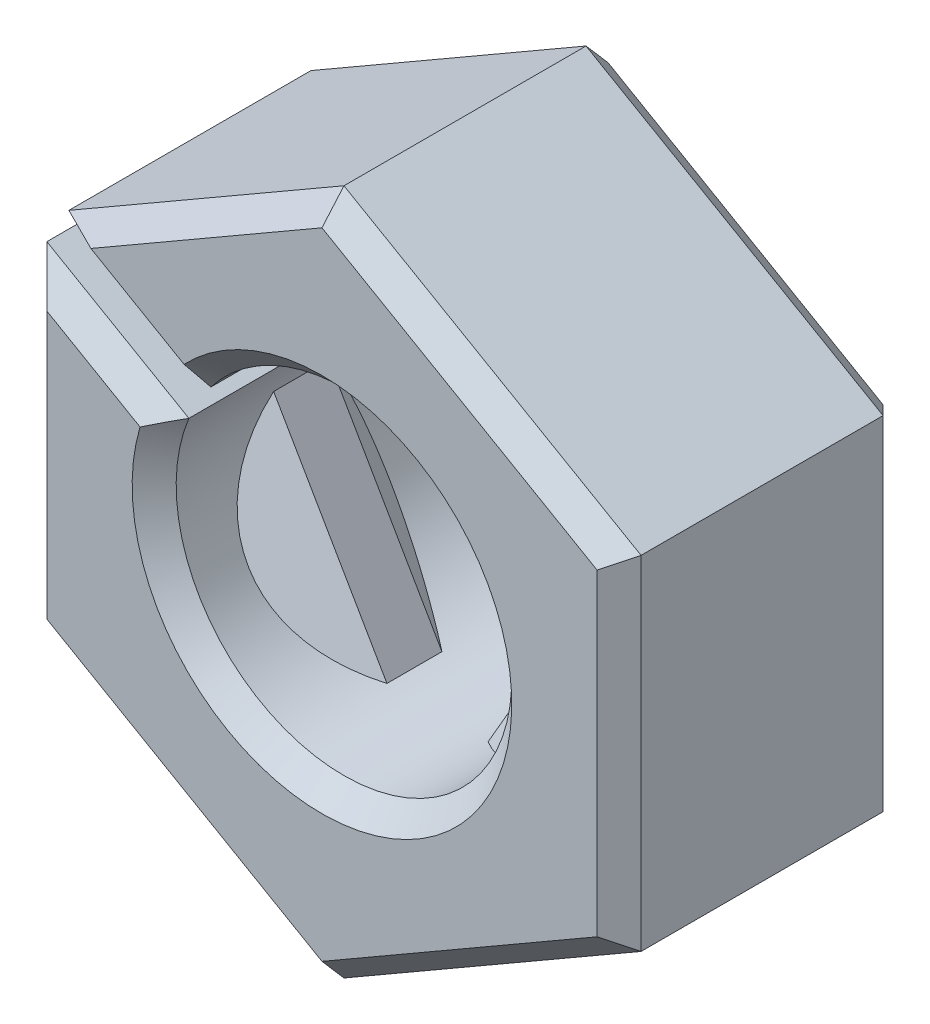
SolidWorks part; units mm, degrees
ref_plane "Front" through (0, 0, 0) normal (0, 0, 1) x (1, 0, 0)
ref_plane "Top" through (0, 0, 0) normal (0, 1, 0) x (1, 0, 0)
ref_plane "Right" through (0, 0, 0) normal (1, 0, 0) x (0, 0, -1)
sketch "Sketch1" plane through (0, 0, 0) normal (0, 0, 1) x (1, 0, 0)
  line L1 (2.7, -1.5588) -> (2.7, 1.5588)
  line L2 (2.7, 1.5588) -> (0, 3.1177)
  line L3 (0, 3.1177) -> (-2.7, 1.5588)
  line L4 (-2.7, 1.5588) -> (-2.7, -1.5588)
  line L5 (-2.7, -1.5588) -> (0, -3.1177)
  line L6 (0, -3.1177) -> (2.7, -1.5588)
  circle A0 centre (0, 0) radius 2.7 construction
  circle A1 centre (0, 0) radius 1.525
  dimension "D1" = 3.05
  dimension "D2" = 5.4
extrude "Boss-Extrude1" add sketch "Sketch1" along normal mid plane 2.6
sketch "Sketch3" plane through (0, 0, 0) normal (1, 0, 0) x (0, 0, -1)
  line L0 (-0.65, 1.525) -> (0.65, 1.525)
  line L1 (1.3, 1.525) -> (-1.3, 1.525) construction
  line L4 (0, 0) -> (0, 1.125) construction
  line L5 (0.65, 1.525) -> (0.25, 1.125)
  line L6 (0.25, 1.125) -> (-0.25, 1.125)
  line L7 (-0.25, 1.125) -> (-0.65, 1.525)
  dimension "D1" = 0.4
  dimension "D2" = 90
  dimension "D3" = 0.5
extrude "Clip" add sketch "Sketch3" along normal up to next and the other way up to next
pattern_circular "Clips x3" count 3 over 360 about axis through (0, 0, 1.3) along (0, 0, 1) of "Clip"
sketch "Sketch4" plane through (0, 0, 0) normal (0, 0, 1) x (1, 0, 0)
  line L0 (-2.7, 1.5588) -> (0, 0)
extrude "Split" cut sketch "Sketch4" against normal through all both and the other way through all thin thin type mid plane wall 0.4
chamfer "Deburs" distance 0.2 angle 45 18 edges at (1.3207, -0.7625, -1.3) (2.7, 0, -1.3) (1.35, 2.3383, -1.3) (-1.25, 2.396, -1.3) (-2.7, -0.1155, -1.3) (-1.35, -2.3383, -1.3) (1.35, -2.3383, -1.3) (1.3207, -0.7625, 1.3) (-1.35, -2.3383, 1.3) (-2.7, -0.1155, 1.3) (-1.25, 2.396, 1.3) (1.35, 2.3383, 1.3) (2.7, 0, 1.3) (1.35, -2.3383, 1.3) (-1.8546, 1.3017, -1.3) (-2.0546, 0.9553, -1.3) (-1.8546, 1.3017, 1.3) (-2.0546, 0.9553, 1.3)
equation "\"D1@Sketch1\"=\"Clearance Hole Diameter@Box Assy.Assembly\"-.1"
equation "\"D2@Sketch1\"=\"Nut Trap Diameter@Box Assy.Assembly\"-0.3mm"
equation "\"D1@Boss-Extrude1\"=\"Nut Trap Depth@Box Assy.Assembly\""
